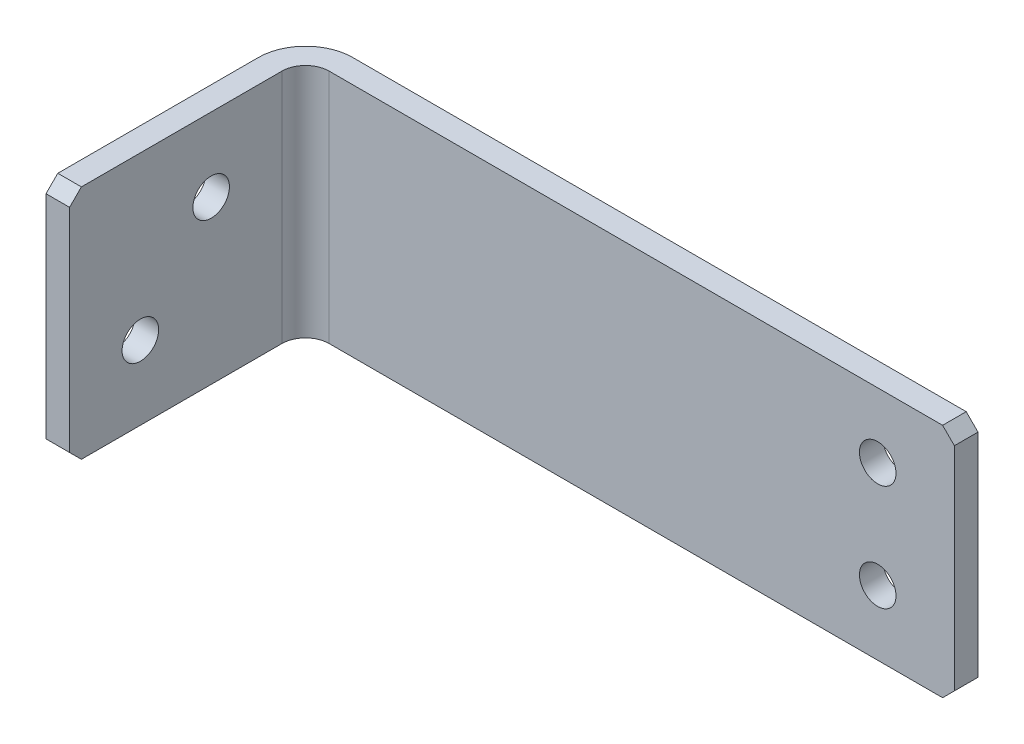
SolidWorks part; units mm, degrees
material "6061 Alloy"
ref_plane "Front Plane" through (0, 0, 0) normal (0, 0, 1) x (1, 0, 0)
ref_plane "Top Plane" through (0, 0, 0) normal (0, 1, 0) x (1, 0, 0)
ref_plane "Right Plane" through (0, 0, 0) normal (1, 0, 0) x (0, 0, -1)
sketch "Sketch1" plane through (0, 0, 0) normal (0, 1, 0) x (1, 0, 0)
  line L0 (0, 0) -> (0, 18)
  line L1 (2, 20) -> (55, 20)
  line L2 (-2, 0) -> (-2, 18)
  line L3 (2, 22) -> (55, 22)
  line L4 (-2, 0) -> (0, 0)
  line L5 (55, 20) -> (55, 22)
  arc A0 (0, 18) -> (2, 20) centre (2, 18) cw
  arc A1 (-2, 18) -> (2, 22) centre (2, 18) cw
  dimension "D1" = 2
  dimension "D2" = 20
  dimension "D3" = 55
  dimension "D4" = 2
extrude "Base" add sketch "Sketch1" along normal blind 20
sketch "Sketch2" plane through (-2, 0, 0) normal (-1, 0, 0) x (0, 0, 1)
  line L0 (0, 20) -> (0, 0) construction
  line L1 (-18, 10) -> (-14.8526, 10) construction
  line L2 (-18, 20) -> (-18, 0) construction
  circle A0 centre (-12, 13.75) radius 1.55
  circle A1 centre (-6, 6.25) radius 1.55
  dimension "D3" = 3.1
  dimension "D1" = 6
  dimension "D2" = 7.5
  dimension "D4" = 6
  dimension "D5" = 3.75
extrude "GuideSideHoles" cut sketch "Sketch2" against normal blind 20
sketch "Sketch3" plane through (0, 0, -22) normal (0, 0, -1) x (-1, 0, 0)
  line L0 (-55, 10) -> (-48.7207, 10) construction
  line L1 (-55, 20) -> (-55, 0) construction
  circle A0 centre (-48.5, 14.5) radius 1.55
  circle A1 centre (-48.5, 5.5) radius 1.55
  dimension "D1" = 9
  dimension "D2" = 3.1
  dimension "D3" = 6.5
extrude "FootSideHoles" cut sketch "Sketch3" against normal through all
chamfer "Chamfer1" distance 1 angle 45 4 edges at (-1, 0, 0) (-1, 20, 0) (55, 0, -21) (55, 20, -21)
sketch "Sketch4" plane through (0, 0, -22) normal (0, 0, -1) x (-1, 0, 0)
  line L0 (2, 20) -> (2, 0) construction
  line L1 (-54, 0) -> (-2, 0) construction
  circle A0 centre (-36, 8) radius 2
  dimension "D3" = 4
  dimension "D1" = 38
  dimension "D2" = 8
extrude "CableTieHole" [suppressed] cut sketch "Sketch4" against normal through all contours A0
